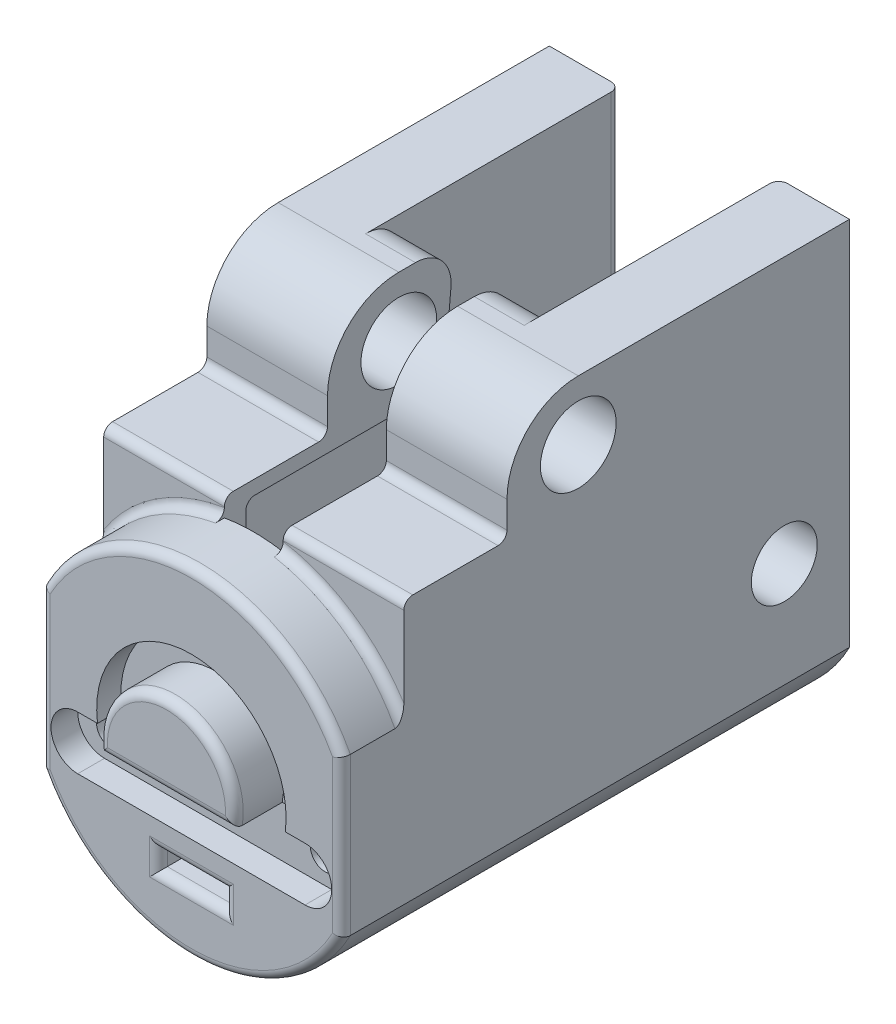
SolidWorks part; units mm, degrees
ref_plane "前视基准面" through (0, 0, 0) normal (0, 0, 1) x (1, 0, 0)
ref_plane "上视基准面" through (0, 0, 0) normal (0, 1, 0) x (1, 0, 0)
ref_plane "右视基准面" through (0, 0, 0) normal (1, 0, 0) x (0, 0, -1)
sketch "草图1" plane through (0, 0, 0) normal (0, 0, 1) x (1, 0, 0)
  line L0 (-7.5, -1.375) -> (7.5, -1.375)
  arc A0 (7.5, -1.375) -> (-7.5, -1.375) centre (0, 0) ccw
  point P6 (0, -1.375)
  point P7 (0, 7.625)
  dimension "D1" = 15
  dimension "D2" = 9
extrude "凸台-拉伸1" add sketch "草图1" along normal blind 5.8
sketch "草图2" plane through (0, 0, 0) normal (0, 0, 1) x (1, 0, 0)
  line L0 (-12.75, -4.375) -> (12.75, -4.375) construction
  line L1 (-12.75, -1.375) -> (12.75, -1.375)
  line L2 (-12.75, -7.375) -> (12.75, -7.375)
  line L3 (-7.5, -1.375) -> (7.5, -1.375) construction
  arc A0 (-12.75, -1.375) -> (-12.75, -7.375) centre (-12.75, -4.375) ccw
  arc A1 (12.75, -7.375) -> (12.75, -1.375) centre (12.75, -4.375) ccw
  circle A3 centre (0, 0) radius 19
  point P2 (0, -4.375)
  dimension "D1" = 6
  dimension "D2" = 25.5
  dimension "D3" = 38
extrude "凸台-拉伸2" add sketch "草图2" along normal blind 3
sketch "草图3" plane through (0, 0, 3) normal (0, 0, 1) x (1, 0, 0)
  line L0 (0, -7.375) -> (0, -10.375)
  line L1 (-12.75, -7.375) -> (12.75, -7.375) construction
  line L2 (-3.7, -10.375) -> (3.7, -10.375)
  line L3 (-3.7, -10.375) -> (-3.7, -12.375)
  line L4 (-3.7, -12.375) -> (3.7, -12.375)
  line L5 (3.7, -12.375) -> (3.7, -10.375)
  point P7 (0, -10.375)
  dimension "D1" = 7.4
  dimension "D2" = 2
  dimension "D3" = 3
extrude "切除-拉伸1" cut sketch "草图3" against normal blind 2.7 contours L4 L5 L2 L3
sketch "草图6" plane through (0, 0, 3) normal (0, 0, 1) x (1, 0, 0)
  line L0 (7.5, -1.375) -> (10.5357, -1.375)
  line L3 (-7.5, -1.375) -> (7.5, -1.375) construction
  line L4 (-10.5357, -1.375) -> (-7.5, -1.375)
  line L6 (-9.6825, -4.375) -> (9.6825, -4.375) construction
  arc A0 (-7.5, -1.375) -> (7.5, -1.375) centre (0, 0) cw
  arc A1 (-10.5357, -1.375) -> (10.5357, -1.375) centre (0, 0) cw
  arc A2 (-9.6825, -4.375) -> (9.6825, -4.375) centre (0, 0) cw construction
  arc A3 (7.5, -1.375) -> (-7.5, -1.375) centre (0, 0) ccw construction
  dimension "D1" = 3
extrude "切除-拉伸2" cut sketch "草图6" against normal blind 2.7
sketch "草图8" plane through (0, 0, 0) normal (0, 0, -1) x (-1, 0, 0)
  line L0 (-12.75, -1.375) -> (12.75, -1.375)
  line L1 (-12.75, -7.375) -> (12.75, -7.375)
  line L2 (0, 55) -> (0, -55) construction
  arc A0 (-12.75, -7.375) -> (-12.75, -1.375) centre (-12.75, -4.375) cw
  arc A1 (12.75, -1.375) -> (12.75, -7.375) centre (12.75, -4.375) cw
  circle A4 centre (0, 0) radius 19
  circle A5 centre (-12, -4.375) radius 1.65
  circle A6 centre (12, -4.375) radius 1.65
  dimension "D1" = 3.3
  dimension "D2" = 24
  dimension "D3" = 38
extrude "凸台-拉伸3" add sketch "草图8" along normal blind 4
sketch "草图11" plane through (0, 0, 0) normal (1, 0, 0) x (0, 0, -1)
  line L0 (4, -19) -> (4, 19) construction
  line L1 (54, -19) -> (54, 19)
  line L2 (54, -19) -> (4, -19)
  line L3 (54, 19) -> (4, 19)
  line L4 (4, -19) -> (4, 19)
  line L5 (54, -19) -> (4, 19) construction
  line L6 (54, 19) -> (4, -19) construction
  line L7 (14, -10) -> (54, -10)
  line L8 (14, 10) -> (54, 10)
  circle A0 centre (14, 0) radius 10
  dimension "D1" = 20
  dimension "D5" = 19
  dimension "D2" = 10
  dimension "D3" = 38
  dimension "D4" = 50
extrude "凸台-拉伸4" add sketch "草图11" along normal mid plane 6 contours A0 L8 L1 L3 L4 | A0 L4 L2 L1 L7
ref_plane "基准面1" through (0, 0, -4) normal (0, 0, -1) x (-1, 0, 0)
sketch "草图14" plane through (0, 0, 0) normal (1, 0, 0) x (0, 0, -1)
  line L0 (4, -18.7617) -> (4, 18.7617) construction
  line L1 (14, 3) -> (46.6886, 3)
  line L3 (4, -19) -> (54, -19)
  line L4 (4, -19) -> (4, 19)
  line L5 (4, 19) -> (54, 19)
  line L6 (54, -19) -> (54, 19)
  circle A0 centre (14, 3) radius 4.25
  circle A1 centre (46.6886, 3) radius 3.7
  dimension "D1" = 8.5
  dimension "D3" = 7.4
  dimension "D2" = 10
  dimension "D4" = 32.6886
  dimension "D5" = 3
extrude "凸台-拉伸5" add sketch "草图14" along normal mid plane 38
sketch "草图16" plane through (0, -19, 0) normal (0, -1, 0) x (1, 0, 0)
  line L0 (-3.3, -4) -> (3.3, -4)
  line L2 (0, -4) -> (-19, -4) construction
  line L3 (19, -4) -> (0, -4) construction
  line L4 (-3.3, -4) -> (-3.3, -54)
  line L5 (19, -54) -> (-19, -54) construction
  line L6 (-3.3, -54) -> (3.3, -54)
  line L7 (3.3, -54) -> (3.3, -4)
  point P7 (0, -4)
  dimension "D1" = 6.6
extrude "切除-拉伸3" cut sketch "草图16" against normal up to surface (38 mm away) up to face at (0, 19, -24)
sketch "草图17" plane through (0, 0, -4) normal (0, 0, 1) x (1, 0, 0)
  circle A0 centre (0, 0) radius 19
extrude "切除-拉伸4" cut sketch "草图17" against normal blind 86 flip side to cut
sketch "草图18" plane through (0, 0, 0) normal (0, 0, 1) x (1, 0, 0)
  circle A0 centre (12, -4.375) radius 1.65
  circle A1 centre (-12, -4.375) radius 1.65
  circle A2 centre (12, -4.375) radius 1.65 construction
  circle A3 centre (-12, -4.375) radius 1.65 construction
  dimension "D3" = 24
extrude "切除-拉伸5" cut sketch "草图18" against normal blind 106
sketch "草图19" plane through (0, 0, -54) normal (0, 0, -1) x (-1, 0, 0)
  circle A0 centre (-12, -4.375) radius 3
  circle A1 centre (12, -4.375) radius 3
  circle A2 centre (12, -4.375) radius 1.65 construction
  dimension "D1" = 6
  dimension "D2" = 6
extrude "切除-拉伸6" cut sketch "草图19" against normal offset from surface (40 mm away) 10 up to plane "基准面1"
sketch "草图22" plane through (0, 0, -54) normal (0, 0, -1) x (-1, 0, 0)
  line L0 (0, 20.9) -> (0, -20.9) construction
  line L1 (-16.8392, 8.8) -> (-16.8392, -8.8)
  line L2 (16.8392, 8.8) -> (16.8392, -8.8)
  arc A0 (-3.3, 18.7112) -> (-3.3, -18.7112) centre (0, 0) ccw construction
  arc A1 (-16.8392, 8.8) -> (-16.8392, -8.8) centre (0, 0) ccw
  arc A2 (16.8392, 8.8) -> (16.8392, -8.8) centre (0, 0) cw
  dimension "D1" = 8.8
extrude "切除-拉伸7" cut sketch "草图22" against normal through all
fillet "圆角2" radius 1 6 edges at (-3.7, -11.375, 3) (0, -12.375, 3) (3.7, -11.375, 3) (0, -10.375, 3) (0, -1.375, 5.8) (0, 7.625, 5.8)
fillet "圆角4" radius 1 4 edges at (0, 19, 3) (0, -19, 3) (-16.8392, 0, 3) (16.8392, 0, 3)
sketch "草图29" plane through (0, 0, 0) normal (1, 0, 0) x (0, 0, -1)
  line L0 (46.6886, 3) -> (14, 3)
  line L1 (46.6886, 3) -> (23.5743, 26.1143)
  line L2 (15.5743, 32.8) -> (15.5743, 20.8)
  line L3 (15.5743, 32.8) -> (54, 32.8)
  line L4 (4, 20.8) -> (4, 8.8)
  line L5 (4, 8.8) -> (54, 8.8)
  line L6 (54, 32.8) -> (54, 8.8)
  line L7 (15.5743, 20.8) -> (4, 20.8)
  circle A0 centre (14, 3) radius 4.25
  circle A1 centre (46.6886, 3) radius 3.7
  circle A2 centre (46.6886, 3) radius 3.7 construction
  circle A3 centre (14, 3) radius 4.25 construction
  arc A4 (23.5743, 26.1143) -> (14, 3) centre (46.6886, 3) ccw
  circle A5 centre (23.5743, 26.1143) radius 4.25
  dimension "D1" = 45
  dimension "D2" = 8.5
  dimension "D4" = 4
  dimension "D3" = 24
  dimension "D5" = 12
  dimension "D6" = 8
  dimension "D7" = 11.5743
extrude "凸台-拉伸6" add sketch "草图29" along normal up to surface and the other way up to surface contours A5 L1 L5 L6 L3 L4 A4 | A5 A4 L5 L1
sketch "草图33" plane through (0, 0, 0) normal (1, 0, 0) x (0, 0, -1)
  line L0 (54, 32.8) -> (54, -18.7112)
  line L1 (54, -18.7112) -> (29.5743, -18.7112)
  line L2 (54, 32.8) -> (29.5743, 32.8)
  line L3 (54, 32.8) -> (15.5743, 32.8) construction
  line L4 (29.5743, 32.8) -> (29.5743, -18.7112)
  line L6 (4, 32.8) -> (29.5743, 32.8)
  line L7 (4, -18.7112) -> (29.5743, -18.7112)
  arc A0 (4, -18.7112) -> (29.5743, 32.8) centre (-35.0894, 32.8) ccw
  point P11 (23.5743, 26.1143)
  dimension "D1" = 6
extrude "切除-拉伸10" cut sketch "草图33" against normal mid plane 17.8
sketch "草图40" plane through (0, 0, 0) normal (1, 0, 0) x (0, 0, -1)
  line L0 (6.4143, -16.7866) -> (6.4143, 19.2134)
  line L1 (6.4143, 19.2134) -> (30.4143, 19.2134)
  line L2 (30.4143, 19.2134) -> (30.4143, -16.7866)
  line L3 (6.4143, -16.7866) -> (54, -16.7866) construction
  line L4 (30.4143, -16.7866) -> (6.4143, -16.7866)
  dimension "D1" = 19.2134
  dimension "D2" = 24
extrude "切除-拉伸17" cut sketch "草图40" against normal mid plane 17.8
sketch "草图34" plane through (0, 0, -4) normal (0, 0, -1) x (-1, 0, 0)
  line L0 (8.9, 32.8) -> (-8.9, 32.8) construction
  line L1 (-3.3, 8.8) -> (3.3, 8.8)
  line L2 (-3.3, 8.8) -> (-3.3, 32.8)
  line L3 (-3.3, 32.8) -> (3.3, 32.8)
  line L4 (3.3, 8.8) -> (3.3, 32.8)
extrude "切除-拉伸12" cut sketch "草图34" along normal up to surface (20.9555 mm away)
fillet "圆角7" radius 4 2 edges at (6.1, 32.8, -29.5743) (-6.1, 32.8, -29.5743)
fillet "圆角8" radius 1 2 edges at (-11.223, 15.3312, -4) (11.223, 15.3312, -4)
fillet "圆角9" radius 1 2 edges at (8.9, 8.0067, -54) (-8.9, 8.0067, -54)
fillet "圆角11" radius 1 4 edges at (-6.1, 19.2134, -28.1308) (6.1, 19.2134, -28.1308) (-6.1, 19.2134, -6.4143) (6.1, 19.2134, -6.4143)
sketch "草图43" plane through (8.9, 0, 0) normal (-1, 0, 0) x (0, 0, 1)
  line L0 (-46.6886, 3) -> (-29.718, -13.9706)
  line L1 (-46.6886, 3) -> (-42.9886, 3)
  line L3 (-29.718, -13.9706) -> (-4, 11.7475)
  line L5 (-29.718, -13.9706) -> (-29.7071, -16.7866)
  line L6 (-6.4143, -16.7866) -> (-53, -16.7866) construction
  line L9 (-4, 18.7112) -> (-4, -18.7112) construction
  line L12 (-29.7071, -16.7866) -> (-4, -16.7866)
  line L13 (-4, -16.7866) -> (-4, 11.7475)
  circle A0 centre (-46.6886, 3) radius 3.7 construction
  dimension "D1" = 45
  dimension "D2" = 24
extrude "凸台-拉伸11" add sketch "草图43" along normal up to surface (17.8 mm away) contours L5 L12 L13 L3
sketch "草图44" plane through (0, 0, -4) normal (0, 0, -1) x (-1, 0, 0)
  line L0 (-8.9, -16.7866) -> (8.9, -16.7866)
  line L2 (3.3, -16.7866) -> (-3.3, -16.7866) construction
  arc A0 (-8.9, -16.7866) -> (8.9, -16.7866) centre (0, 0) ccw
  dimension "D1" = 19
extrude "凸台-拉伸12" add sketch "草图44" along normal up to surface (25.7071 mm away)
sketch "草图46" plane through (16.8392, 0, 0) normal (1, 0, 0) x (0, 0, -1)
  circle A0 centre (14, 3) radius 4.25
  dimension "D1" = 8.5
extrude "凸台-拉伸13" add sketch "草图46" against normal up to surface (7.9392 mm away)
sketch "草图47" plane through (-16.8392, 0, 0) normal (-1, 0, 0) x (0, 0, 1)
  circle A0 centre (-14, 3) radius 4.25
  dimension "D1" = 8.5
extrude "凸台-拉伸14" add sketch "草图47" against normal up to surface (7.9392 mm away) up to face at (-8.9, 3, -50.3886)
fillet "圆角12" radius 1 7 edges at (0, 11.7475, -4) (-6.1, 9.3332, -6.4143) (6.1, 9.3332, -6.4143) (-10.0696, 20.8, -4) (10.0696, 20.8, -4) (-10.0696, 20.8, -15.5743) (10.0696, 20.8, -15.5743)
fillet "圆角14" radius 8 2 edges at (-10.0696, 32.8, -15.5743) (10.0696, 32.8, -15.5743)
